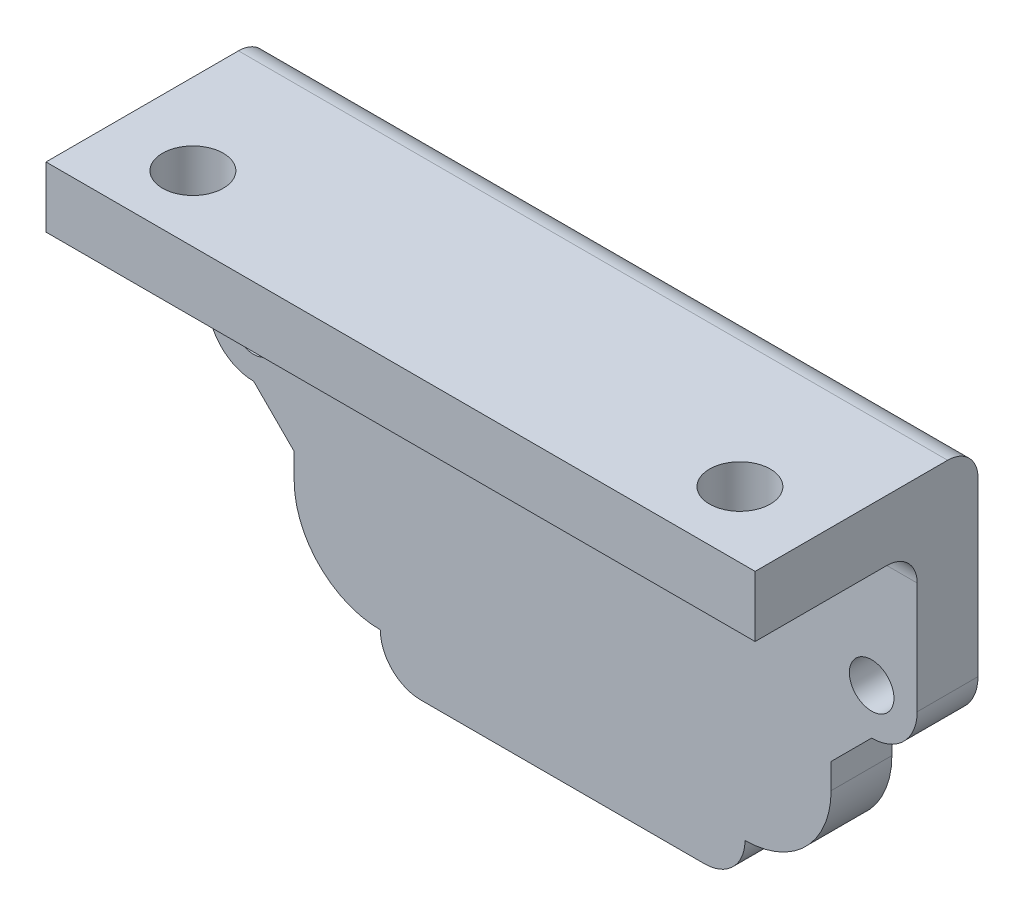
SolidWorks part; units mm, degrees
ref_plane "前视基准面" through (0, 0, 0) normal (0, 0, 1) x (1, 0, 0)
ref_plane "上视基准面" through (0, 0, 0) normal (0, 1, 0) x (1, 0, 0)
ref_plane "右视基准面" through (0, 0, 0) normal (1, 0, 0) x (0, 0, -1)
sketch "草图1" plane through (0, 0, 0) normal (0, 0, 1) x (1, 0, 0)
  line L2 (-13.25, -3.875) -> (-13.25, -2.625)
  line L3 (-13.25, 8.625) -> (13.25, 8.625)
  line L4 (13.25, -3.875) -> (13.25, -2.625)
  line L9 (-17.5, 1.625) -> (-17.5, 8.625)
  line L10 (-17.5, 8.625) -> (-13.25, 8.625)
  line L11 (17.5, 1.625) -> (17.5, 8.625)
  line L12 (13.25, 8.625) -> (17.5, 8.625)
  line L13 (-15.25, -0.625) -> (-13.25, -2.625)
  line L14 (15.25, -0.625) -> (13.25, -2.625)
  line L16 (9, -8.125) -> (9, -10.125)
  line L17 (9, -10.125) -> (-9, -10.125)
  line L18 (-9, -10.125) -> (-9, -8.125)
  circle A0 centre (-15.25, 1.625) radius 1.1
  circle A1 centre (15.25, 1.625) radius 1.1
  arc A2 (-17.5, 1.625) -> (-15.25, -0.625) centre (-15.25, 1.625) ccw
  arc A3 (15.25, -0.625) -> (17.5, 1.625) centre (15.25, 1.625) ccw
  arc A4 (-13.25, -3.875) -> (-9, -8.125) centre (-9, -3.875) ccw
  arc A5 (9, -8.125) -> (13.25, -3.875) centre (9, -3.875) ccw
  point P0 (0, 0)
extrude "凸台-拉伸1" add sketch "草图1" along normal blind 3
sketch "草图2" plane through (0, 8.625, 0) normal (0, 1, 0) x (1, 0, 0)
  line L0 (17.5, 0) -> (-17.5, 0)
  line L1 (-17.5, 0) -> (-17.5, -11)
  line L2 (-17.5, -11) -> (17.5, -11)
  line L3 (17.5, -11) -> (17.5, 0)
extrude "凸台-拉伸2" add sketch "草图2" along normal blind 3
fillet "圆角1" radius 1.5 2 edges at (0, 8.625, 3) (0, 11.625, 0)
sketch "草图3" plane through (0, 8.625, 0) normal (0, -1, 0) x (1, 0, 0)
  circle A0 centre (13.5, 7.75) radius 1.5
  circle A1 centre (-13.5, 7.75) radius 1.5
extrude "切除-拉伸1" cut sketch "草图3" against normal blind 3
fillet "圆角2" radius 2 2 edges at (9, -10.125, 1.5) (-9, -10.125, 1.5)
